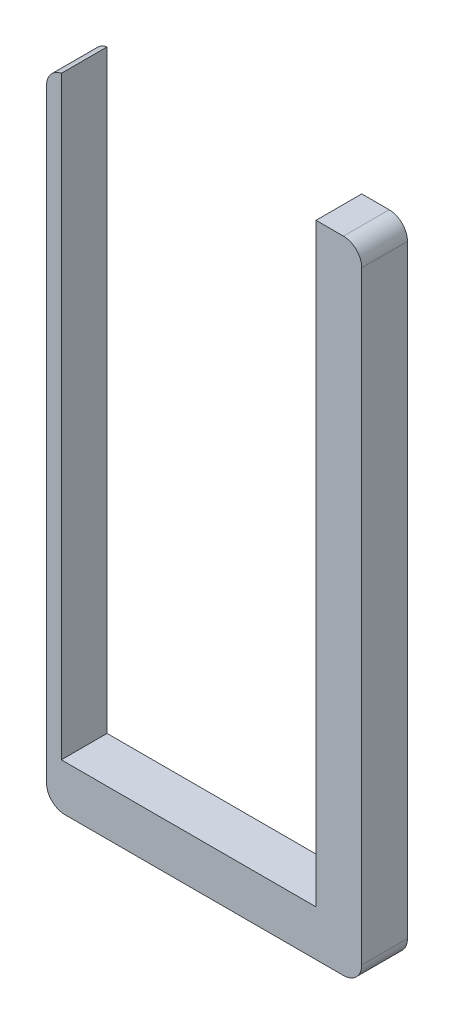
SolidWorks part; units mm, degrees
ref_plane "Front Plane" through (0, 0, 0) normal (0, 0, 1) x (1, 0, 0)
ref_plane "Top Plane" through (0, 0, 0) normal (0, 1, 0) x (1, 0, 0)
ref_plane "Right Plane" through (0, 0, 0) normal (1, 0, 0) x (0, 0, -1)
sketch "Sketch1" plane through (0, 0, 0) normal (0, 0, 1) x (1, 0, 0)
  line L0 (0, 0) -> (35.3568, 0)
  line L1 (35.3568, 0) -> (35.3568, 82.55)
  line L2 (35.3568, 82.55) -> (41.7068, 82.55)
  line L3 (41.7068, 82.55) -> (41.7068, -6.35)
  line L4 (41.7068, -6.35) -> (-2.0574, -6.35)
  line L5 (-2.0574, -6.35) -> (-2.0574, 82.55)
  line L6 (-2.0574, 82.55) -> (0, 82.55)
  line L7 (0, 82.55) -> (0, 0)
  point P3 (-1.0287, 82.55)
  dimension "D1" = 2.0574
  dimension "D2" = 35.3568
  dimension "D3" = 6.35
  dimension "D4" = 88.9
  dimension "D5" = 88.9
  dimension "D6" = 6.35
extrude "Boss-Extrude1" add sketch "Sketch1" along normal blind 6.35
fillet "Fillet1" radius 2.54 4 edges at (41.7068, 82.55, 3.175) (-2.0574, 82.55, 3.175) (-2.0574, -6.35, 3.175) (41.7068, -6.35, 3.175)
